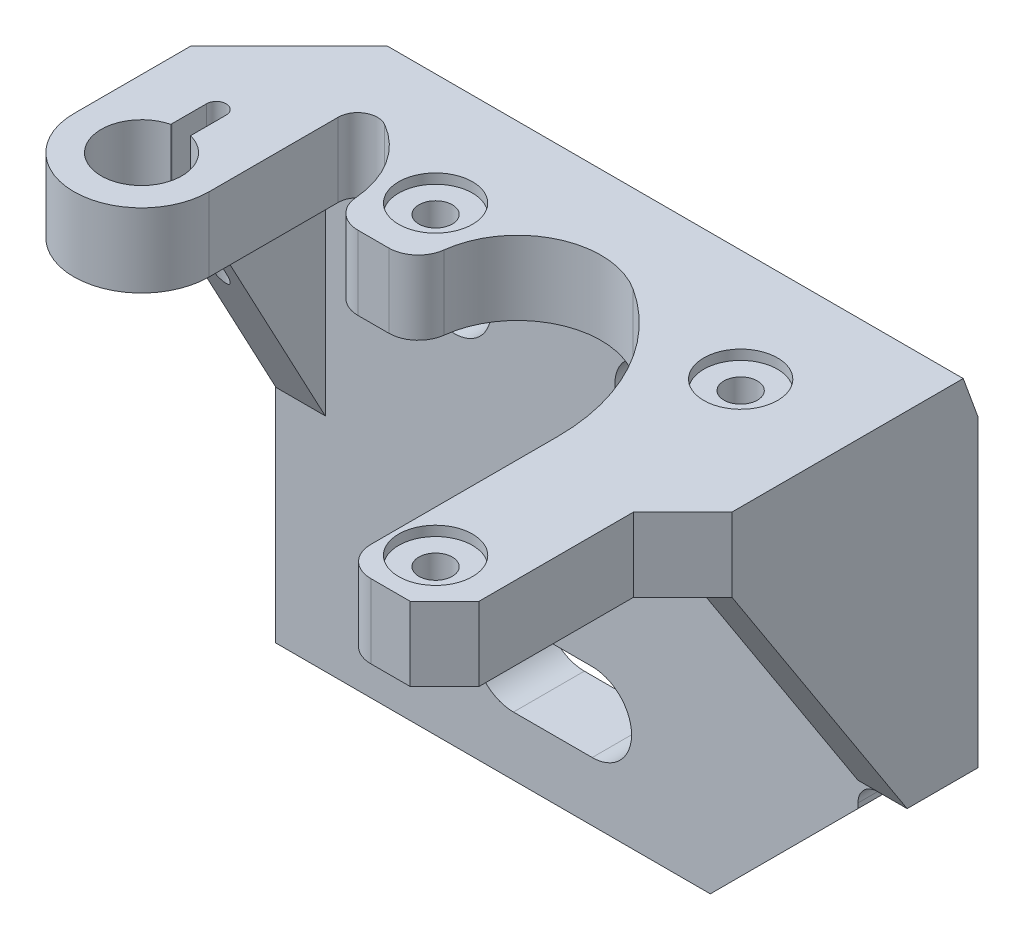
SolidWorks part; units mm, degrees
material "ABS"
ref_plane "Płaszczyzna przednia" through (0, 0, 0) normal (0, 0, 1) x (1, 0, 0)
ref_plane "Płaszczyzna górna" through (0, 0, 0) normal (0, 1, 0) x (1, 0, 0)
ref_plane "Płaszczyzna prawa" through (0, 0, 0) normal (1, 0, 0) x (0, 0, -1)
sketch "Szkic1" plane through (0, 0, 0) normal (0, 0, 1) x (1, 0, 0)
  line L0 (0, -10) -> (0, 10) construction
  line L1 (-10, 10) -> (10, 10) construction
  line L3 (-34, 22.5) -> (31, 22.5)
  line L4 (-34, 22.5) -> (-34, -30)
  line L5 (-34, -30) -> (31, -30)
  line L6 (31, 22.5) -> (31, -30)
  circle A0 centre (10, 10) radius 1.7
  circle A1 centre (-10, 10) radius 1.7
  circle A2 centre (0, -10) radius 1.7
  point P4 (0, 0)
  point P8 (0, 10)
  dimension "D1" = 3.4
  dimension "D2" = 20
  dimension "D3" = 20
  dimension "D4" = 24
  dimension "D5" = 21
  dimension "D6" = 20
  dimension "D7" = 12.5
extrude "Dodanie-wyciągnięcie1" add sketch "Szkic1" along normal blind 7.2
sketch "Szkic2" plane through (0, 0, 0) normal (0, 0, -1) x (-1, 0, 0)
  line L1 (-31, -30) -> (-8.8, -30)
  line L2 (-31, -30) -> (-31, -12.8)
  line L3 (-31, -12.8) -> (-8.8, -12.8)
  line L4 (-8.8, -30) -> (-8.8, -12.8)
  circle A0 centre (0, -10) radius 1.7 construction
  dimension "D1" = 8.8
  dimension "D2" = 2.8
extrude "Wytnij-wyciągnięcie1" cut sketch "Szkic2" against normal blind 3.4
fillet "Zaokrąglenie1" radius 2 1 edges at (8.8, -21.4, 3.4)
sketch "Szkic3" plane through (0, 0, 7.2) normal (0, 0, -1) x (-1, 0, 0)
  circle A0 centre (-10, 10) radius 3.7
  circle A1 centre (10, 10) radius 3.7
  circle A2 centre (0, -10) radius 3.7
  dimension "D1" = 7.4
extrude "Wytnij-wyciągnięcie2" cut sketch "Szkic3" along normal blind 3.3
sketch "Szkic4" plane through (0, 0, 7.2) normal (0, 0, 1) x (1, 0, 0)
  line L1 (31, 22.5) -> (20.5, 22.5)
  line L2 (31, 22.5) -> (31, 15)
  line L3 (31, 15) -> (20.5, 15)
  line L4 (20.5, 22.5) -> (20.5, 15)
  point P4 (10, 10)
  dimension "D1" = 10.5
  dimension "D2" = 5
extrude "Dodanie-wyciągnięcie2" add sketch "Szkic4" along normal blind 42
sketch "Szkic5" plane through (0, 22.5, 0) normal (0, 1, 0) x (1, 0, 0)
  line L0 (24.75, -43.865) -> (24.75, -12.865) construction
  line L1 (24.75, -12.865) -> (24.75, -7.2) construction
  line L2 (24.75, -7.2) -> (10, -7.2) construction
  line L3 (6.3, -7.2) -> (13.7, -7.2) construction
  circle A0 centre (24.75, -12.865) radius 3.75
  circle A1 centre (24.75, -43.865) radius 3.75
  dimension "D1" = 14.75
  dimension "D2" = 7.5
  dimension "D3" = 5.665
  dimension "D4" = 31
extrude "Wytnij-wyciągnięcie3" cut sketch "Szkic5" against normal blind 1
sketch "Szkic6" plane through (0, 21.5, 0) normal (0, 1, 0) x (1, 0, 0)
  circle A0 centre (24.75, -43.865) radius 1.7
  circle A1 centre (24.75, -12.865) radius 1.7
  dimension "D1" = 3.4
extrude "Wytnij-wyciągnięcie4" cut sketch "Szkic6" against normal up to next
fillet "Zaokrąglenie2" radius 20 1 edges at (20.5, 18.75, 7.2)
chamfer "Sfazowanie1" distance 3.5 angle 45 1 edges at (31, 18.75, 49.2)
sketch "Szkic7" plane through (0, 0, 7.2) normal (0, 0, 1) x (1, 0, 0)
  line L0 (0.5, 22.5) -> (-34, 22.5) construction
  line L1 (-1.75, 22.5) -> (-10.75, 22.5)
  line L2 (-1.75, 22.5) -> (-1.75, 15)
  line L3 (-1.75, 15) -> (-10.75, 15)
  line L4 (-10.75, 22.5) -> (-10.75, 15)
  line L5 (0.5, 15) -> (31, 15) construction
  line L6 (-34, 22.5) -> (-34, -30) construction
  dimension "D1" = 23.25
  dimension "D2" = 9
extrude "Dodanie-wyciągnięcie3" add sketch "Szkic7" along normal blind 12
sketch "Szkic8" plane through (0, 22.5, 0) normal (0, 1, 0) x (1, 0, 0)
  line L0 (24.75, -43.865) -> (24.75, -12.865) construction
  line L1 (24.75, -12.865) -> (-6.25, -12.865) construction
  circle A0 centre (-6.25, -12.865) radius 1.7
  circle A1 centre (24.75, -12.865) radius 1.7 construction
extrude "Wytnij-wyciągnięcie5" cut sketch "Szkic8" against normal up to next
sketch "Szkic9" plane through (0, 22.5, 0) normal (0, 1, 0) x (1, 0, 0)
  circle A0 centre (-6.25, -12.865) radius 3.75
  circle A1 centre (24.75, -12.865) radius 3.75 construction
extrude "Wytnij-wyciągnięcie6" cut sketch "Szkic9" against normal up to surface (1 mm away) up to face at (24.75, 21.5, 14.565)
fillet "Zaokrąglenie3" radius 10 2 edges at (-1.75, 18.75, 7.2) (-10.75, 18.75, 7.2)
fillet "Zaokrąglenie4" radius 8.5 1 edges at (5.0524, 18.75, 7.725)
sketch "Szkic10" plane through (31, 0, 0) normal (1, 0, 0) x (0, 0, -1)
  line L0 (0, 22.5) -> (-25, 22.5)
  line L2 (-25, 22.5) -> (-25, 15)
  line L3 (-45.7, 15) -> (-7.2, 15) construction
  line L4 (-25, 15) -> (-7.2, -12.5)
  line L5 (-7.2, -30) -> (-7.2, 15) construction
  line L6 (-7.2, -12.5) -> (0, -12.5)
  line L7 (0, -12.8) -> (0, 22.5) construction
  line L8 (0, -12.5) -> (0, 22.5)
  dimension "D1" = 35
  dimension "D2" = 25
extrude "Dodanie-wyciągnięcie4" add sketch "Szkic10" along normal blind 5
chamfer "Sfazowanie2" distance 5 angle 45 1 edges at (31, 18.75, 25)
fillet "Zaokrąglenie5" radius 3 3 edges at (-1.75, 18.75, 19.2) (-10.75, 18.75, 19.2) (20.5, 18.75, 49.2)
chamfer "Sfazowanie3" distance 15 angle 45 1 edges at (31, -30, 5.3)
chamfer "Sfazowanie4" distance 5 angle 45 1 edges at (-34, -30, 3.6)
chamfer "Sfazowanie5" distance 1.5 angle 70 1 edges at (1, 22.5, 0) first distance on face at (-6.25, 22.5, 16.615)
fillet "Zaokrąglenie6" radius 2 1 edges at (31, -12.5, 3.6)
sketch "Szkic11" plane through (0, 22.5, 0) normal (0, 1, 0) x (1, 0, 0)
  line L0 (-34, 0) -> (36, 0) construction
  line L1 (-25.625, -19.27) -> (-25.625, -15.77) construction
  line L2 (-26.625, -19.27) -> (-26.625, -15.77)
  line L3 (-24.625, -19.27) -> (-24.625, -15.77)
  line L4 (-34, -7.2) -> (-34, -1.5) construction
  line L5 (-32.5, -7.2) -> (-32.5, -23.37)
  line L6 (-20.75, -7.2) -> (-34, -7.2) construction
  line L7 (-18.75, -23.37) -> (-18.75, -7.402)
  line L8 (-20.75, -7.2) -> (-32.5, -7.2)
  circle A0 centre (-25.625, -23.37) radius 4.1
  arc A1 (-26.625, -19.27) -> (-24.625, -19.27) centre (-25.625, -19.27) ccw
  arc A2 (-24.625, -15.77) -> (-26.625, -15.77) centre (-25.625, -15.77) ccw
  arc A3 (-32.5, -23.37) -> (-18.75, -23.37) centre (-25.625, -23.37) ccw
  arc A4 (-10.7796, -16.4308) -> (-20.75, -7.2) centre (-20.75, -17.2) ccw construction
  arc A5 (-18.75, -7.402) -> (-20.75, -7.2) centre (-20.75, -17.2) ccw
  point P2 (-25.625, -17.52)
  line M13 (-34, -7.2) -> (-20.75, -7.2)
  arc M14 (-20.75, -7.2) -> (-10.7796, -16.4308) centre (-20.75, -17.2) cw
  dimension "D1" = 8.2
  dimension "D3" = 1
  dimension "D6" = 1.5
  dimension "D2" = 23.37
  dimension "D4" = 3.5
  dimension "D7" = 13.75
extrude "Dodanie-wyciągnięcie5" add sketch "Szkic11" against normal blind 7.5 contours L5 A3 L7 A2 L3 A1 A0 L2 M14 M13 region at (-26.625, 22.5, 7.4684)
ref_plane "Płaszczyzna1" through (-25.625, 0, 0) normal (-1, 0, 0) x (0, 0, 1)
sketch "Szkic12" plane through (-25.625, 0, 0) normal (-1, 0, 0) x (0, 0, 1)
  line L0 (19.2, 15) -> (7.2, -7.5)
  line L1 (7.2, 15) -> (23.37, 15) construction
  line L2 (7.2, 22.5) -> (7.2, -25) construction
  line L3 (19.2, 15) -> (7.2, 15)
  line L4 (7.2, 15) -> (7.2, -7.5)
  dimension "D1" = 22.5
  dimension "D2" = 12
extrude "Dodanie-wyciągnięcie6" add sketch "Szkic12" along normal mid plane 5
sketch "Szkic13" plane through (0, 15, 0) normal (0, 1, 0) x (1, 0, 0)
  line L3 (-26.625, -15.77) -> (-26.625, -19.2)
  line L4 (-26.625, -19.2) -> (-24.625, -19.2)
  line L5 (-24.625, -19.2) -> (-24.625, -15.77)
  line L6 (-26.625, -15.77) -> (-26.625, -19.2)
  line L7 (-26.625, -19.2) -> (-24.625, -19.2)
  line L8 (-24.625, -19.2) -> (-24.625, -15.77)
  arc A1 (-24.625, -15.77) -> (-26.625, -15.77) centre (-25.625, -15.77) ccw
  arc A2 (-24.625, -15.77) -> (-26.625, -15.77) centre (-25.625, -15.77) ccw
  dimension "D1" = 0
extrude "Wytnij-wyciągnięcie7" cut sketch "Szkic13" against normal up to next
fillet "Zaokrąglenie7" radius 2 2 edges at (-32.5, 18.75, 7.2) (-18.75, 18.75, 7.402)
sketch "Szkic14" plane through (0, 0, 0) normal (0, 0, -1) x (-1, 0, 0)
  line L0 (-4, -24) -> (4, -24) construction
  line L1 (4, -16) -> (-4, -16) construction
  line L2 (-4, -24) -> (4, -24)
  line L3 (4, -16) -> (-4, -16)
  arc A0 (4, -24) -> (4, -16) centre (4, -20) ccw construction
  arc A1 (-4, -16) -> (-4, -24) centre (-4, -20) ccw construction
  arc A2 (4, -24) -> (4, -16) centre (4, -20) ccw
  arc A3 (-4, -16) -> (-4, -24) centre (-4, -20) ccw
extrude "Wytnij-wyciągnięcie8" cut sketch "Szkic14" against normal up to next
chamfer "Sfazowanie6" distance 13 angle 45 1 edges at (-34, -3.3106, 0)
sketch "Szkic15" plane through (0, 0, 0) normal (0, 0, -1) x (-1, 0, 0)
  line L0 (-23, -12.8) -> (-23, -5.3) construction
  line L1 (-8.8, -12.8) -> (-31.9464, -12.8) construction
  line L2 (-10.8, -12.8) -> (-31.9464, -12.8) construction
  line L3 (-28, 2.2) -> (-18, 2.2)
  line L4 (-28, 2.2) -> (-28, -12.8)
  line L5 (-28, -12.8) -> (-18, -12.8)
  line L6 (-18, 2.2) -> (-18, -12.8)
  line L7 (-23, -12.8) -> (-23, 2.2) construction
  line L8 (-28, -5.3) -> (-18, -5.3) construction
  dimension "D1" = 10
  dimension "D2" = 23
  dimension "D3" = 15
extrude "Wytnij-wyciągnięcie9" cut sketch "Szkic15" against normal up to surface (3.4 mm away) up to face at (21.8876, -19.1629, 3.4)
